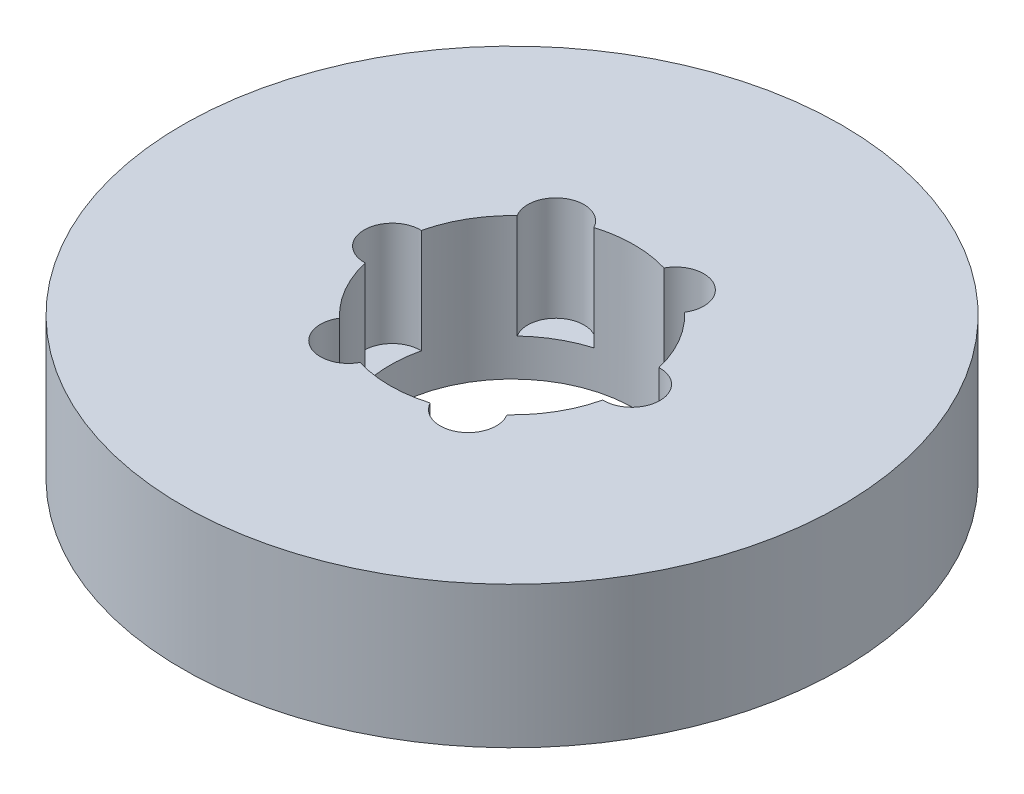
SolidWorks part; units mm, degrees
ref_plane "Front Plane" through (0, 0, 0) normal (0, 0, 1) x (1, 0, 0)
ref_plane "Top Plane" through (0, 0, 0) normal (0, 1, 0) x (1, 0, 0)
ref_plane "Right Plane" through (0, 0, 0) normal (1, 0, 0) x (0, 0, -1)
sketch "Sketch1" plane through (0, 0, 0) normal (0, 1, 0) x (1, 0, 0)
  circle A0 centre (0, 0) radius 67.5
  dimension "FLANGE_OD" = 135
extrude "Boss-Extrude1" add sketch "Sketch1" along normal blind 29
sketch "Sketch2" plane through (0, 0, 0) normal (0, 1, 0) x (1, 0, 0)
  circle A0 centre (0, 0) radius 25
  dimension "BORE_D" = 50
extrude "Cut-Extrude1" cut sketch "Sketch2" along normal through all
sketch "Sketch3" plane through (0, 29, 0) normal (0, 1, 0) x (1, 0, 0)
  circle A0 centre (0, 0) radius 24.5236 construction
  circle A1 centre (-24.5236, 0) radius 5.7594
  dimension "BOLT_D" = 11.5189
  dimension "BOLT_PCD" = 49.0471
extrude "Cut-Extrude2" cut sketch "Sketch3" against normal blind 21.3564
pattern_circular "CirPattern1" count 6 over 360 about axis through (0, 0, 0) along (0, 1, 0) of "Cut-Extrude2"
